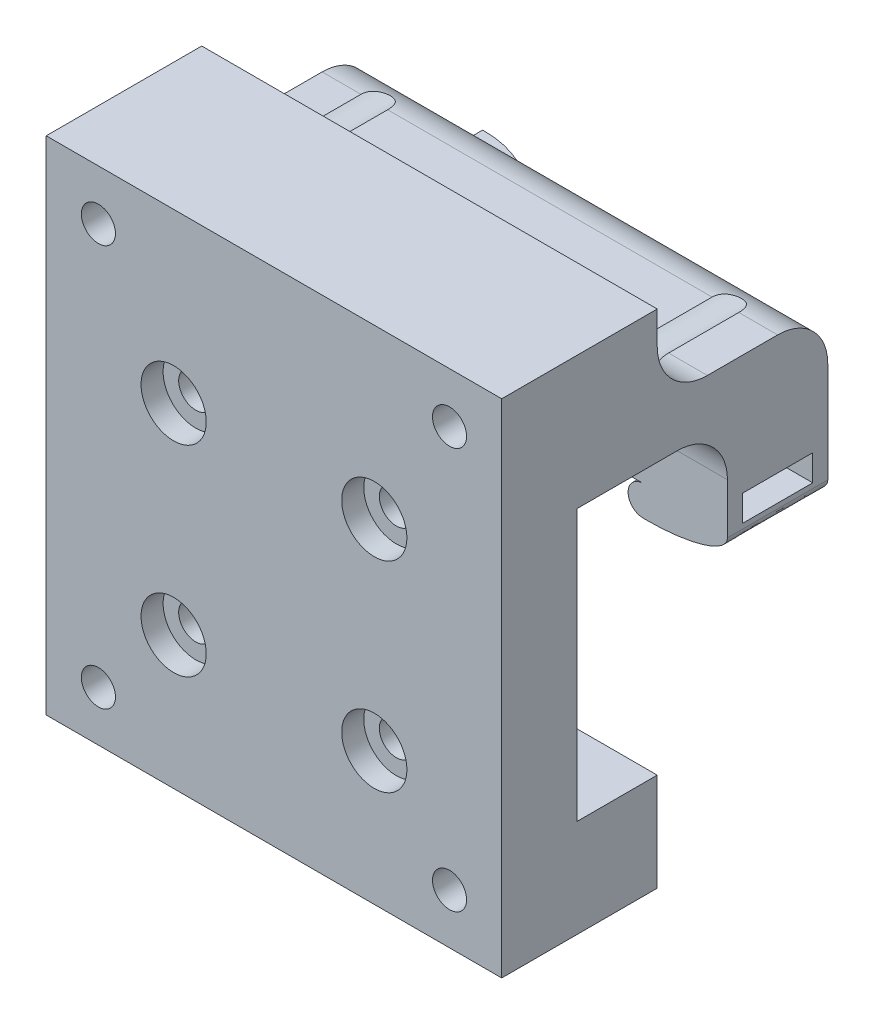
SolidWorks part; units mm, degrees
ref_plane "Front Plane" through (0, 0, 0) normal (0, 0, 1) x (1, 0, 0)
ref_plane "Top Plane" through (0, 0, 0) normal (0, 1, 0) x (1, 0, 0)
ref_plane "Right Plane" through (0, 0, 0) normal (1, 0, 0) x (0, 0, -1)
sketch "Sketch1" plane through (0, 0, 0) normal (0, 0, 1) x (1, 0, 0)
  line L1 (0, 0) -> (45.4, 0)
  line L2 (0, 0) -> (0, 50)
  line L3 (0, 50) -> (45.4, 50)
  line L4 (45.4, 0) -> (45.4, 50)
  dimension "D1" = 45.4
  dimension "D2" = 50
extrude "Boss-Extrude1" add sketch "Sketch1" along normal blind 15.5
sketch "Sketch2" plane through (0, 0, 0) normal (0, 0, -1) x (-1, 0, 0)
  line L0 (-45.4, 0) -> (-45.4, 50) construction
  line L1 (-45.4, 36.7633) -> (0, 36.7633)
  line L2 (-45.4, 36.7633) -> (-45.4, 9.7633)
  line L3 (-45.4, 9.7633) -> (0, 9.7633)
  line L4 (0, 36.7633) -> (0, 9.7633)
  line L5 (0, 50) -> (0, 0) construction
  dimension "D1" = 27
extrude "Cut-Extrude1" cut sketch "Sketch2" against normal blind 8
sketch "Sketch7" plane through (0, 0, 0) normal (0, 0, -1) x (-1, 0, 0)
  line L1 (-45.4, 41.7633) -> (0, 41.7633)
  line L2 (-45.4, 41.7633) -> (-45.4, 36.7633)
  line L3 (-45.4, 36.7633) -> (0, 36.7633)
  line L4 (0, 41.7633) -> (0, 36.7633)
  dimension "D1" = 5
extrude "Boss-Extrude2" add sketch "Sketch7" along normal blind 17
sketch "Sketch8" plane through (0, 36.7633, 0) normal (0, -1, 0) x (1, 0, 0)
  line L1 (0, -17) -> (45.4, -17)
  line L2 (0, -17) -> (0, -7)
  line L3 (0, -7) -> (45.4, -7)
  line L4 (45.4, -17) -> (45.4, -7)
  line L5 (45.4, -17) -> (45.4, 0) construction
  point P5 (45.4, -6)
  dimension "D1" = 10
extrude "Boss-Extrude3" add sketch "Sketch8" along normal blind 12.52
sketch "Sketch10" plane through (0, 0, -17) normal (0, 0, -1) x (-1, 0, 0)
  line L0 (0, 27.2433) -> (-45.4, 27.2433) construction
  line L1 (0, 24.2433) -> (0, 41.7633) construction
  line L2 (-45.4, 41.7633) -> (-45.4, 24.2433) construction
  line L3 (0, 24.2433) -> (-45.4, 24.2433) construction
  line L5 (-37, 27.2433) -> (-8, 27.2433)
  line L7 (-37, 24.2433) -> (-8, 24.2433)
  arc A0 (-37, 27.2433) -> (-37, 24.2433) centre (-37, 25.7433) cw
  arc A1 (-8, 27.2433) -> (-8, 24.2433) centre (-8, 25.7433) ccw
  dimension "D1" = 3
extrude "Cut-Extrude2" cut sketch "Sketch10" against normal up to next
sketch "Sketch11" plane through (45.4, 0, 0) normal (1, 0, 0) x (0, 0, -1)
  line L1 (8.5, 27.2433) -> (15.5, 27.2433)
  line L2 (8.5, 27.2433) -> (8.5, 29.8433)
  line L3 (8.5, 29.8433) -> (15.5, 29.8433)
  line L4 (15.5, 27.2433) -> (15.5, 29.8433)
  line L5 (7, 24.2433) -> (7, 36.7633) construction
  line L6 (17, 41.7633) -> (17, 24.2433) construction
  line L7 (17, 24.2433) -> (7, 24.2433) construction
  dimension "D1" = 1.5
  dimension "D2" = 1.5
  dimension "D3" = 2.6
  dimension "D4" = 3
extrude "Cut-Extrude3" cut sketch "Sketch11" against normal through all
fillet "Fillet1" radius 2.5 2 edges at (0, 24.2433, -12) (45.4, 24.2433, -12) second distance 8 first distance on face at (0, 28.5433, -12) first distance on face at (45.4, 28.5433, -12)
sketch "Sketch13" plane through (0, 0, 15.5) normal (0, 0, 1) x (1, 0, 0)
  circle A0 centre (12.7, 33.2632) radius 1.7
  circle A1 centre (32.7, 33.2632) radius 1.7
  circle A2 centre (32.7, 13.2632) radius 1.7
  circle A3 centre (12.7, 13.2632) radius 1.7
  dimension "D1" = 3.4
extrude "Cut-Extrude4" cut sketch "Sketch13" against normal up to next
sketch "Sketch14" plane through (0, 0, -17) normal (0, 0, -1) x (-1, 0, 0)
  line L0 (0, 26.7433) -> (0, 41.7633) construction
  line L1 (0, 28.7433) -> (-8, 28.7433)
  line L2 (0, 28.7433) -> (0, 27.2433)
  line L3 (0, 27.2433) -> (-8, 27.2433)
  line L4 (-8, 28.7433) -> (-8, 27.2433)
  line L5 (0, 28.7433) -> (-8, 27.2433) construction
  line L6 (0, 27.2433) -> (-8, 28.7433) construction
  line L7 (-8, 27.2433) -> (-37, 27.2433) construction
  point P4 (-4, 27.9933)
  dimension "D1" = 1.5
  dimension "D2" = 8
extrude "Boss-Extrude4" add sketch "Sketch14" along normal blind 11
fillet "Fillet3" radius 10 1 edges at (8, 27.9933, -17)
fillet "Fillet4" radius 10 1 edges at (8, 27.9933, -28)
sketch "Sketch15" plane through (0, 0, 15.5) normal (0, 0, -1) x (-1, 0, 0)
  line L0 (-22.7, 50) -> (-22.7, 0) construction
  line L1 (-40.2, 5) -> (-5.2, 5) construction
  line L2 (-40.2, 5) -> (-40.2, 45) construction
  line L3 (-40.2, 45) -> (-5.2, 45) construction
  line L4 (-5.2, 5) -> (-5.2, 45) construction
  line L5 (-40.2, 5) -> (-5.2, 45) construction
  line L6 (-40.2, 45) -> (-5.2, 5) construction
  line L7 (-45.4, 50) -> (0, 50) construction
  line L8 (0, 0) -> (-45.4, 0) construction
  line L9 (0, 25) -> (-45.4, 25) construction
  line L12 (0, 50) -> (0, 0) construction
  line L13 (-45.4, 0) -> (-45.4, 50) construction
  circle A0 centre (-5.2, 45) radius 1.7
  circle A1 centre (-40.2, 45) radius 1.7
  circle A2 centre (-40.2, 5) radius 1.7
  circle A3 centre (-5.2, 5) radius 1.7
  point P4 (-22.7, 25)
  dimension "D3" = 3.4
  dimension "D1" = 40
  dimension "D2" = 35
extrude "Cut-Extrude6" cut sketch "Sketch15" along normal through all
ref_plane "Plane1" through (0, 0, 12.5) normal (0, 0, 1) x (1, 0, 0)
sketch "Sketch16" plane through (0, 0, 12.5) normal (0, 0, 1) x (1, 0, 0)
  circle A0 centre (5.2, 45) radius 3.5
  circle A1 centre (40.2, 45) radius 3.5
  circle A2 centre (40.2, 5) radius 3.5
  circle A3 centre (5.2, 5) radius 3.5
  dimension "D1" = 7
extrude "Cut-Extrude7" cut sketch "Sketch16" against normal through all
sketch "Sketch17" plane through (0, 0, 15.5) normal (0, 0, 1) x (1, 0, 0)
  circle A0 centre (12.7, 33.2632) radius 3.25
  circle A1 centre (32.7, 33.2632) radius 3.25
  circle A2 centre (32.7, 13.2632) radius 3.25
  circle A3 centre (12.7, 13.2632) radius 3.25
  dimension "D1" = 6.5
extrude "Cut-Extrude8" cut sketch "Sketch17" against normal blind 2.2
fillet "Fillet5" radius 5 1 edges at (22.7, 36.7633, -7)
fillet "Fillet6" radius 5 1 edges at (22.7, 41.7633, -17)
fillet "Fillet7" radius 5 3 edges at (1.9341, 41.7633, 0) (43.4659, 41.7633, 0) (22.7, 41.7633, 0)
sketch "Sketch18" plane through (0, 0, 0) normal (0, 0, -1) x (-1, 0, 0)
  line L0 (-45.4, 4.8816) -> (0, 4.8816) construction
  line L1 (-45.4, 0) -> (-45.4, 9.7633) construction
  line L2 (0, 9.7633) -> (0, 0) construction
  circle A0 centre (-32.4, 4.8816) radius 1.35
  circle A1 centre (-13, 4.8816) radius 1.35
  dimension "D1" = 2.7
  dimension "D2" = 13
  dimension "D3" = 13
extrude "Cut-Extrude9" cut sketch "Sketch18" against normal blind 10
